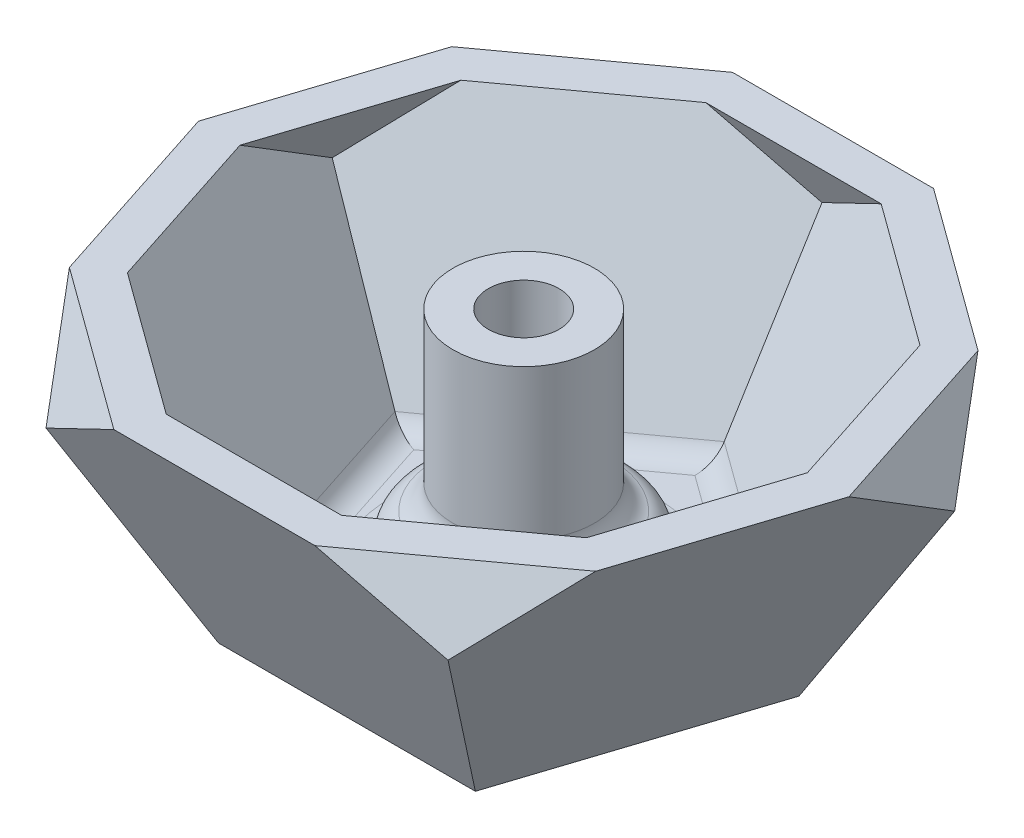
SolidWorks part; units mm, degrees
ref_plane "Front Plane" through (0, 0, 0) normal (0, 0, 1) x (1, 0, 0)
ref_plane "Top Plane" through (0, 0, 0) normal (0, 1, 0) x (1, 0, 0)
ref_plane "Right Plane" through (0, 0, 0) normal (1, 0, 0) x (0, 0, -1)
sketch "Sketch1" plane through (0, 0, 0) normal (0, 1, 0) x (1, 0, 0)
  line L1 (0, 12.3607) -> (-11.7557, 3.8197)
  line L2 (-11.7557, 3.8197) -> (-7.2654, -10)
  line L3 (-7.2654, -10) -> (7.2654, -10)
  line L4 (7.2654, -10) -> (11.7557, 3.8197)
  line L5 (11.7557, 3.8197) -> (0, 12.3607)
  circle A0 centre (0, 0) radius 10 construction
  dimension "D1" = 20
extrude "Boss-Extrude1" add sketch "Sketch1" along normal blind 30 draft 26.565 draft outward yes
sketch "Sketch3" plane through (0, 30, 0) normal (0, 1, 0) x (1, 0, 0)
  line L0 (0, 0) -> (14.6946, 20.2254) construction
  line L1 (7.2654, 10) -> (-7.2654, 10)
  line L2 (-7.2654, 10) -> (-11.7557, -3.8197)
  line L3 (-11.7557, -3.8197) -> (0, -12.3607)
  line L4 (0, -12.3607) -> (11.7557, -3.8197)
  line L5 (11.7557, -3.8197) -> (7.2654, 10)
  line L6 (29.3893, 9.5492) -> (0, 30.9017) construction
  circle A0 centre (0, 0) radius 10 construction
  dimension "D1" = 20
extrude "Cut-Extrude1" cut sketch "Sketch3" against normal blind 30 draft 26.565 flip side to cut
sketch "Sketch4" plane through (0, 0, 0) normal (1, 0, 0) x (0, 0, -1)
  line L0 (-3.8197, 30) -> (-3.8197, 0) construction
  line L1 (-10, 0) -> (3.8197, 0) construction
  point P5 (-3.8197, 15)
ref_plane "Plane1" through (0, 15, 0) normal (0, 1, 0) x (1, 0, 0)
sketch "Sketch5" plane through (0, 15, 0) normal (0, 1, 0) x (1, 0, 0)
  circle A0 centre (0, 0) radius 19.3475
extrude "Cut-Extrude2" cut sketch "Sketch5" along normal blind 25
shell "Shell1" thickness 2 removed face at (0, 15, 0)
sketch "Sketch6" plane through (0, 2, 0) normal (0, 1, 0) x (1, 0, 0)
  circle A0 centre (0, 0) radius 4
  circle A1 centre (0, 0) radius 2
  dimension "D1" = 8
  dimension "D2" = 4
extrude "Boss-Extrude2" add sketch "Sketch6" along direction (0, 1, 0) on the side of the normal up to surface (13 mm away) up to face at (0, 15, 0)
sketch "Sketch10" plane through (0, 2, 0) normal (0, 1, 0) x (1, 0, 0)
  line L1 (0, 5.1962) -> (-4.5, 2.5981)
  line L2 (-4.5, 2.5981) -> (-4.5, -2.5981)
  line L3 (-4.5, -2.5981) -> (0, -5.1962)
  line L4 (0, -5.1962) -> (4.5, -2.5981)
  line L5 (4.5, -2.5981) -> (4.5, 2.5981)
  line L6 (4.5, 2.5981) -> (0, 5.1962)
  circle A3 centre (0, 0) radius 4.5 construction
  circle A5 centre (0, 0) radius 4 construction
  circle A6 centre (0, 0) radius 4
  circle A7 centre (0, 0) radius 6
  circle A8 centre (0, 0) radius 4.5
  point P5 (0, 0)
  circle M18 centre (0, 0) radius 4
  dimension "D1" = 12
  dimension "D2" = 9
extrude "Boss-Extrude4" add sketch "Sketch10" along normal blind 3 contours A8 M18 | A8 L1 L2 | A8 L2 L3 | A7 L6 L5 L4 L3 L2 L1 | A8 L3 L4 | A8 L4 L5 | A8 L5 L6 | A8 L6 L1 region at (0, 2, -4.651) region at (-4.0279, 2, -2.3255) region at (0, 2, -4.3727) region at (4.0279, 2, -2.3255) region at (-4.0279, 2, 2.3255) region at (4.0279, 2, 2.3255) region at (0, 2, 4.651) region at (-5.8303, 2, 0)
fillet "Fillet5" radius 1.5 7 edges at (5.1513, 2, -7.0902) (8.335, 2, 2.7082) (0, 2, 8.7639) (-8.335, 2, 2.7082) (-5.1513, 2, -7.0902) (0, 2, 6) (0, 5, 4)
extrude "Cut-Extrude3" cut sketch "Sketch10<3>" against normal up to surface (2 mm away) and the other way blind 2 contours A8 L3 L4 | A8 L2 L3 | A8 L4 L5 | A8 M18 | A8 L1 L2 | A8 L6 L1 | A8 L5 L6 | M18 region at (0, 2, -4.651) region at (-4.0279, 2, -2.3255) region at (0, 2, -4.3727) region at (4.0279, 2, -2.3255) region at (-4.0279, 2, 2.3255) region at (4.0279, 2, 2.3255) region at (0, 2, 4.651) region at (0, 2, 0) up to face at (0, 0, 0)
sketch "Sketch10<3>" plane through (0, 2, 0) normal (0, 1, 0) x (1, 0, 0) same geometry as "Sketch10"
fillet "Fillet6" radius 1.5 7 edges at (0, 5, 6) (4.5, 4, 0) (2.25, 4, 3.8971) (-2.25, 4, 3.8971) (-4.5, 4, 0) (-2.25, 4, -3.8971) (2.25, 4, -3.8971)
